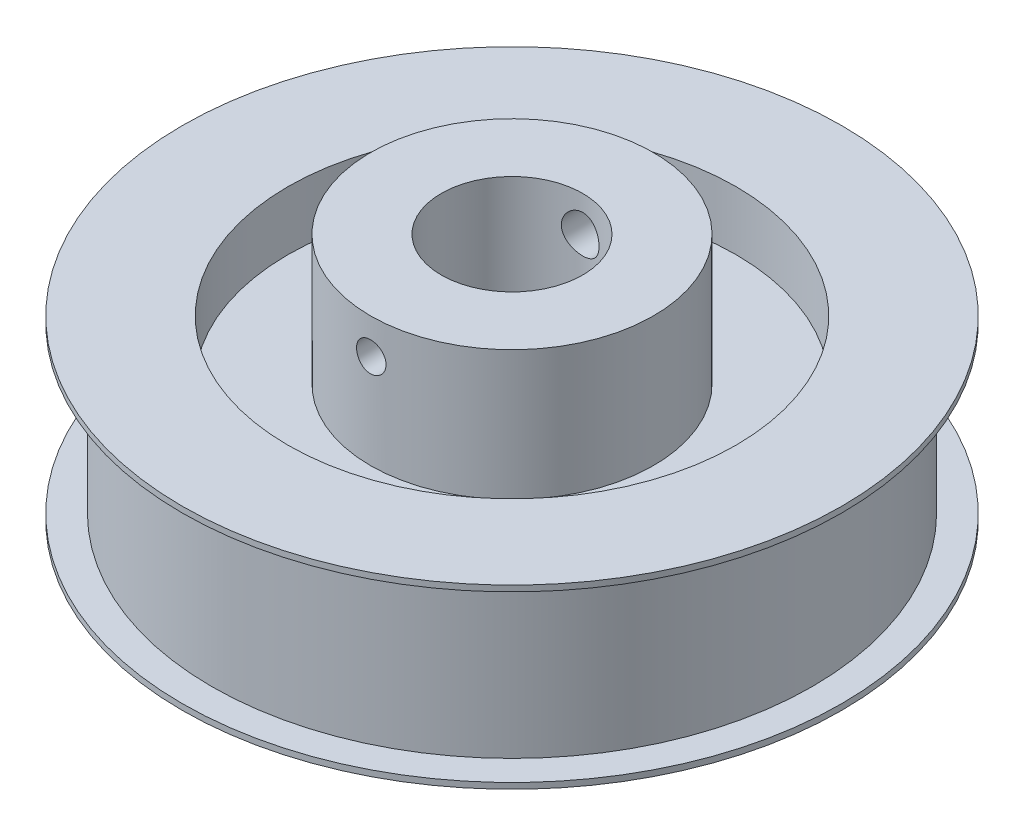
SolidWorks part; units mm, degrees
ref_plane "Alzado" through (0, 0, 0) normal (1, 0, 0) x (0, 1, 0)
ref_plane "Planta" through (0, 0, 0) normal (0, 0, 1) x (0, 1, 0)
ref_plane "Vista lateral" through (0, 0, 0) normal (0, 1, 0) x (-1, 0, 0)
sketch "Croquis1" plane through (0, 0, 0) normal (0, 1, 0) x (-1, 0, 0)
  circle A0 centre (0, 0) radius 25.465
  dimension "D1" = 50.93
extrude "Saliente-Extruir1" add sketch "Croquis1" along normal mid plane 15
sketch "Croquis2" plane through (0, 7.5, 0) normal (0, 1, 0) x (-1, 0, 0)
  circle A3 centre (0, 0) radius 27.965
  dimension "D1" = 55.93
extrude "Saliente-Extruir2" add sketch "Croquis2" against normal blind 0.5
extrude "Saliente-Extruir3" add sketch "Croquis2<2>" along normal blind 0.5 from surface starting at face at (0, -7.5, 25.465)
sketch "Croquis2<2>" plane through (0, 7.5, 0) normal (0, 1, 0) x (-1, 0, 0) same geometry as "Croquis2"
sketch "Croquis3" plane through (0, -7.5, 0) normal (0, 1, 0) x (-1, 0, 0)
  circle A0 centre (0, 0) radius 19
  dimension "D1" = 38
extrude "Saliente-Extruir4" add sketch "Croquis3" along normal blind 21
sketch "Croquis4" plane through (0, -7, 0) normal (0, 1, 0) x (-1, 0, 0)
  circle A0 centre (0, 0) radius 6
  dimension "D1" = 12
extrude "Cortar-Extruir1" cut sketch "Croquis4" against normal through all both and the other way through all
sketch "Croquis5" plane through (0, 13.5, 0) normal (0, 1, 0) x (-1, 0, 0)
  circle A0 centre (0, 0) radius 12
  circle A2 centre (0, 0) radius 19 construction
  circle A3 centre (0, 0) radius 19
  dimension "D1" = 24
extrude "Cortar-Extruir2" cut sketch "Croquis5" against normal offset from surface (11 mm away) 10 up to face at (0, -7.5, 6)
ref_plane "Plano1" through (0, 0, 12) normal (0, 0, 1) x (1, 0, 0)
sketch "Croquis6" plane through (-12, 0, 12) normal (0, 0, -1) x (0, 1, 0)
  line L0 (13.5, 24) -> (7.5, 24) construction
  line L1 (7.5, -15.965) -> (7.5, 39.965) construction
  line L2 (13.5, 24) -> (2.5, 24) construction
  line L3 (10.5, 24) -> (10.5, 0) construction
  line L4 (2.5, 0) -> (13.5, 0) construction
  point P11 (10.5, 12)
hole_wizard "Taladro roscado M31" positions "Croquis6" profile "Croquis7" tap size "M3" standard "DIN" end condition up to next
sketch "Croquis7" plane through (0, 10.5, 12) normal (1, 0, 0) x (0, -1, 0)
  line L0 (0, 0) -> (0, 6)
  line L1 (0, 6) -> (1.25, 6)
  line L2 (1.25, 6) -> (1.25, 0)
  line L5 (1.25, 0) -> (0, 0)
  line L11 (0, -6.35) -> (0, 107.95) construction
  dimension "Diámetro de perforador para roscar hasta el siguiente" = 2.5
  dimension "Profundidad de perforador para roscar hasta el siguiente" = 6
cosmetic thread "Rosca de taladro1" parameters "D2"=3
ref_plane "Plano2" through (0, 0, 0) normal (0, 0, 1) x (1, 0, 0)
sketch "Croquis8" plane through (0, 0, 0) normal (0, 0, 1) x (1, 0, 0)
  circle A0 centre (0, 10.5) radius 1.25 construction
  circle A1 centre (0, 10.5) radius 1.25
ref_axis "Eje2" through (0, 10.5, -21.2911) along (0, 0, 1)
ref_plane "Plano3" through (0, 12, 0) normal (0, -1, 0) x (-1, 0, 0)
sketch "Croquis9" plane through (0, 12, 0) normal (0, 0, 1) x (-1, 0, 0)
  circle A0 centre (0, 1.5) radius 1.25 construction
  circle A1 centre (0, 1.5) radius 1.25 construction
  point P4 (0, 1.5)
hole_wizard "Taladro de margen para M32" positions "Croquis9" profile "Croquis10" hole size "M3" standard "Ansi Metric" end condition up to next
sketch "Croquis10" plane through (0, 10.5, 0) normal (1, 0, 0) x (0, -1, 0)
  line L0 (0, 0) -> (0, 12)
  line L1 (0, 12) -> (1.6, 12)
  line L2 (1.6, 12) -> (1.6, 0)
  line L5 (1.6, 0) -> (0, 0)
  line L11 (0, -6.35) -> (0, 107.95) construction
  dimension "Diámetro de taladro hasta el siguiente" = 3.2
  dimension "Profundidad de taladro hasta el siguiente" = 12
equation "\"Dp\"= 50.93"
equation "\"D1@Croquis1\"=\"Dp\""
equation "\"Dm\"= 38"
equation "\"De\"= \"Dp\" + 5"
equation "\"F\"= 15"
equation "\"L\"= 21"
equation "\"D1@Croquis2\"=\"De\""
equation "\"D1@Saliente-Extruir1\"=\"F\""
equation "\"D1@Saliente-Extruir4\"=\"L\""
equation "\"deje\"=12"
equation "\"D1@Croquis4\"=\"deje\""
equation "\"D1@Croquis3\"=\"Dm\""
